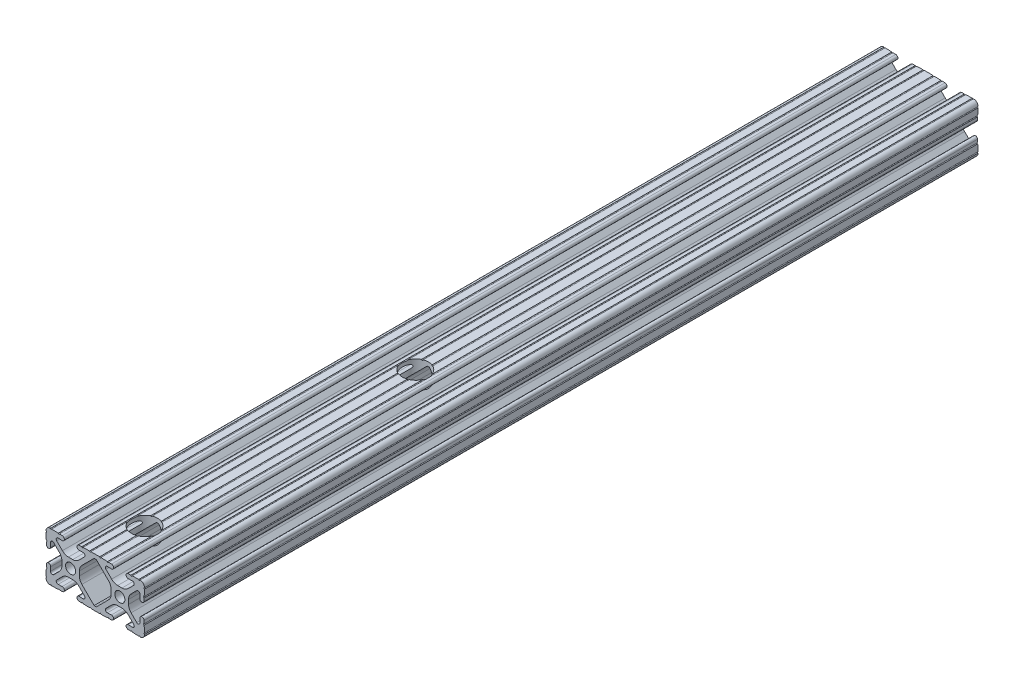
SolidWorks part; units mm, degrees
ref_plane "Front Plane" through (0, 0, 0) normal (0, 0, 1) x (1, 0, 0)
ref_plane "Top Plane" through (0, 0, 0) normal (0, 1, 0) x (1, 0, 0)
ref_plane "Right Plane" through (0, 0, 0) normal (1, 0, 0) x (0, 0, -1)
sketch "Sketch1" plane through (0, 0, 0) normal (0, 0, 1) x (1, 0, 0)
  line L0 (0, 12.7) -> (-12.7814, 12.7) construction
  line L1 (-4.5085, 0) -> (-4.5085, 2.9459)
  line L2 (-6.0437, 12.5461) -> (-10.0976, 12.6876) construction
  line L3 (-11.5616, 12.4229) -> (-4.3159, 12.1699) construction
  line L4 (-6.4364, 10.3486) -> (-6.3592, 12.5571) construction
  line L6 (-2.9459, 4.5085) -> (0, 4.5085)
  line L7 (0, 0) -> (0, 12.7) construction
  line L8 (0, 0) -> (-12.7814, 0) construction
  line L9 (0.7813, 0.7813) -> (-0.7813, -0.7813) construction
  line L10 (-2.9459, 4.5085) -> (-7.1484, 8.711)
  line L11 (-4.5085, 2.9459) -> (-8.711, 7.1484)
  line L13 (0, 0) -> (-12.7814, 12.7814) construction
  line L14 (-10.4131, 12.6987) -> (-4.3048, 12.4853)
  line L15 (-4.3048, 12.4853) -> (-4.382, 10.2769) construction
  line L16 (-4.382, 10.2769) -> (-6.4364, 10.3486)
  line L17 (-12.6987, 10.4131) -> (-12.4853, 4.3048)
  line L18 (-10.2769, 4.382) -> (-10.3486, 6.4364)
  circle A0 centre (0, 0) radius 2.6035
  arc A1 (-4.382, 10.2769) -> (-4.3048, 12.4853) centre (-4.3434, 11.3811) ccw
  arc A2 (-7.1484, 8.711) -> (-6.4364, 10.3486) centre (-6.4698, 9.3896) cw
  arc A3 (-8.711, 7.1484) -> (-10.3486, 6.4364) centre (-9.3896, 6.4698) ccw
  arc A4 (-10.2769, 4.382) -> (-12.4853, 4.3048) centre (-11.3811, 4.3434) cw
  arc A5 (-10.4131, 12.6987) -> (-12.6987, 10.4131) centre (-10.4902, 10.4902) ccw
  arc A6 (-10.4131, 12.6987) -> (-9.7821, 12.6766) centre (-10.0976, 12.6876) ccw
  arc A7 (-6.3592, 12.5571) -> (-5.7282, 12.5351) centre (-6.0437, 12.5461) ccw
  arc A8 (-12.5571, 6.3592) -> (-12.5351, 5.7282) centre (-12.5461, 6.0437) cw
  arc A9 (-12.6987, 10.4131) -> (-12.6766, 9.7821) centre (-12.6876, 10.0976) cw
  dimension "D1" = 5.207
  dimension "D5" = 14.859
  dimension "D9" = 2
  dimension "D2" = 25.4
  dimension "D12" = 0.6314
  dimension "D10" = 2.2098
  dimension "D3" = 9.017
  dimension "D4" = 9.017
  dimension "D6" = 25.4
  dimension "D7" = 6.477
  dimension "D8" = 2.2098
  dimension "D11" = 12.7
sketch "Sketch3" plane through (0, 0, 0) normal (0, 0, 1) x (1, 0, 0)
  line L0 (-2.9459, 4.5085) -> (0, 4.5085) construction
  line L1 (-2.9459, 4.5085) -> (-7.1484, 8.711) construction
  line L2 (-4.382, 10.2769) -> (-6.4364, 10.3486) construction
  line L3 (-10.4131, 12.6987) -> (-4.3048, 12.4853) construction
  line L4 (-4.5085, 0) -> (-4.5085, 2.9459) construction
  line L5 (-4.5085, 2.9459) -> (-8.711, 7.1484) construction
  line L6 (-10.2769, 4.382) -> (-10.3486, 6.4364) construction
  line L7 (-12.6987, 10.4131) -> (-12.4853, 4.3048) construction
  line L8 (-1.1153, 4.5085) -> (1.1153, 4.5085)
  line L9 (-4.2404, 5.803) -> (-7.1484, 8.711)
  line L10 (-4.382, 10.2769) -> (-6.4364, 10.3486)
  line L11 (-9.7821, 12.6766) -> (-6.3592, 12.5571)
  line L12 (-4.5085, -1.1153) -> (-4.5085, 1.1153)
  line L13 (-5.803, 4.2404) -> (-8.711, 7.1484)
  line L14 (-10.2769, 4.382) -> (-10.3486, 6.4364)
  line L15 (-12.6766, 9.7821) -> (-12.5571, 6.3592)
  line L16 (-5.7282, 12.5351) -> (-4.3048, 12.4853)
  line L17 (-12.5351, 5.7282) -> (-12.4853, 4.3048)
  line L18 (0, 0) -> (0, 12.7) construction
  line L19 (0, 0) -> (-12.7814, 0) construction
  line L20 (0, 0) -> (12.7, 0) construction
  line L21 (5.7282, 12.5351) -> (4.3048, 12.4853)
  line L22 (12.7, 10.5674) -> (12.7, 12.6987) construction
  line L23 (10.4131, 12.6987) -> (14.9869, 12.6987)
  line L24 (5.803, 4.2404) -> (12.1093, 10.5467)
  line L25 (4.5085, -1.1153) -> (4.5085, 1.1153)
  line L26 (9.7821, 12.6766) -> (6.3592, 12.5571)
  line L27 (4.382, 10.2769) -> (6.4364, 10.3486)
  line L28 (4.2404, 5.803) -> (7.1484, 8.711)
  line L29 (4.2404, -5.803) -> (7.1484, -8.711)
  line L30 (4.382, -10.2769) -> (6.4364, -10.3486)
  line L31 (9.7821, -12.6766) -> (6.3592, -12.5571)
  line L32 (5.803, -4.2404) -> (12.1093, -10.5467)
  line L33 (12.1093, 10.5467) -> (12.7, 10.5674)
  line L34 (10.4131, -12.6987) -> (14.9869, -12.6987)
  line L35 (5.7282, -12.5351) -> (4.3048, -12.4853)
  line L36 (12.7, -10.5674) -> (12.7, -12.6987) construction
  line L37 (-12.5351, -5.7282) -> (-12.4853, -4.3048)
  line L38 (-5.7282, -12.5351) -> (-4.3048, -12.4853)
  line L39 (-12.6766, -9.7821) -> (-12.5571, -6.3592)
  line L40 (-10.2769, -4.382) -> (-10.3486, -6.4364)
  line L41 (-5.803, -4.2404) -> (-8.711, -7.1484)
  line L42 (-9.7821, -12.6766) -> (-6.3592, -12.5571)
  line L43 (-4.382, -10.2769) -> (-6.4364, -10.3486)
  line L44 (-4.2404, -5.803) -> (-7.1484, -8.711)
  line L45 (-1.1153, -4.5085) -> (1.1153, -4.5085)
  line L46 (12.1093, -10.5467) -> (12.7, -10.5674)
  line L47 (13.2907, -10.5467) -> (12.7, -10.5674)
  line L48 (26.5153, -4.5085) -> (24.2847, -4.5085)
  line L49 (29.6404, -5.803) -> (32.5484, -8.711)
  line L50 (29.782, -10.2769) -> (31.8364, -10.3486)
  line L51 (35.1821, -12.6766) -> (31.7592, -12.5571)
  line L52 (31.203, -4.2404) -> (34.111, -7.1484)
  line L53 (35.6769, -4.382) -> (35.7486, -6.4364)
  line L54 (38.0766, -9.7821) -> (37.9571, -6.3592)
  line L55 (31.1282, -12.5351) -> (29.7048, -12.4853)
  line L56 (37.9351, -5.7282) -> (37.8853, -4.3048)
  line L57 (19.6718, -12.5351) -> (21.0952, -12.4853)
  line L58 (13.2907, 10.5467) -> (12.7, 10.5674)
  line L59 (19.597, -4.2404) -> (13.2907, -10.5467)
  line L60 (15.6179, -12.6766) -> (19.0408, -12.5571)
  line L61 (21.018, -10.2769) -> (18.9636, -10.3486)
  line L62 (21.1596, -5.803) -> (18.2516, -8.711)
  line L63 (21.1596, 5.803) -> (18.2516, 8.711)
  line L64 (21.018, 10.2769) -> (18.9636, 10.3486)
  line L65 (15.6179, 12.6766) -> (19.0408, 12.5571)
  line L66 (20.8915, -1.1153) -> (20.8915, 1.1153)
  line L67 (19.597, 4.2404) -> (13.2907, 10.5467)
  line L68 (19.6718, 12.5351) -> (21.0952, 12.4853)
  line L69 (37.9351, 5.7282) -> (37.8853, 4.3048)
  line L70 (31.1282, 12.5351) -> (29.7048, 12.4853)
  line L71 (38.0766, 9.7821) -> (37.9571, 6.3592)
  line L72 (35.6769, 4.382) -> (35.7486, 6.4364)
  line L73 (31.203, 4.2404) -> (34.111, 7.1484)
  line L74 (29.9085, -1.1153) -> (29.9085, 1.1153)
  line L75 (35.1821, 12.6766) -> (31.7592, 12.5571)
  line L76 (29.782, 10.2769) -> (31.8364, 10.3486)
  line L77 (29.6404, 5.803) -> (32.5484, 8.711)
  line L78 (26.5153, 4.5085) -> (24.2847, 4.5085)
  arc A0 (-10.4131, 12.6987) -> (-9.7821, 12.6766) centre (-10.0976, 12.6876) ccw construction
  arc A1 (-6.4364, 10.3486) -> (-7.1484, 8.711) centre (-6.4698, 9.3896) ccw construction
  arc A2 (-4.382, 10.2769) -> (-4.3048, 12.4853) centre (-4.3434, 11.3811) ccw construction
  arc A3 (-8.711, 7.1484) -> (-10.3486, 6.4364) centre (-9.3896, 6.4698) ccw construction
  arc A4 (-12.4853, 4.3048) -> (-10.2769, 4.382) centre (-11.3811, 4.3434) ccw construction
  arc A5 (-6.3592, 12.5571) -> (-5.7282, 12.5351) centre (-6.0437, 12.5461) ccw construction
  arc A6 (-10.4131, 12.6987) -> (-12.6987, 10.4131) centre (-10.4902, 10.4902) ccw construction
  arc A7 (-12.6766, 9.7821) -> (-12.6987, 10.4131) centre (-12.6876, 10.0976) ccw construction
  arc A8 (-12.5351, 5.7282) -> (-12.5571, 6.3592) centre (-12.5461, 6.0437) ccw construction
  arc A9 (-10.4131, 12.6987) -> (-9.7821, 12.6766) centre (-10.0976, 12.6876) ccw
  arc A10 (-6.4364, 10.3486) -> (-7.1484, 8.711) centre (-6.4698, 9.3896) ccw
  arc A11 (-4.382, 10.2769) -> (-4.3048, 12.4853) centre (-4.3434, 11.3811) ccw
  arc A12 (-8.711, 7.1484) -> (-10.3486, 6.4364) centre (-9.3896, 6.4698) ccw
  arc A13 (-12.4853, 4.3048) -> (-10.2769, 4.382) centre (-11.3811, 4.3434) ccw
  arc A14 (-6.3592, 12.5571) -> (-5.7282, 12.5351) centre (-6.0437, 12.5461) ccw
  arc A15 (-10.4131, 12.6987) -> (-12.6987, 10.4131) centre (-10.4902, 10.4902) ccw
  arc A16 (-12.6766, 9.7821) -> (-12.6987, 10.4131) centre (-12.6876, 10.0976) ccw
  arc A17 (-12.5351, 5.7282) -> (-12.5571, 6.3592) centre (-12.5461, 6.0437) ccw
  arc A18 (-1.1153, 4.5085) -> (-4.2404, 5.803) centre (-1.1153, 8.9281) cw
  arc A19 (4.5085, 1.1153) -> (5.803, 4.2404) centre (8.9281, 1.1153) cw
  arc A20 (1.1153, 4.5085) -> (4.2404, 5.803) centre (1.1153, 8.9281) ccw
  arc A21 (-4.5085, 1.1153) -> (-5.803, 4.2404) centre (-8.9281, 1.1153) ccw
  circle A22 centre (25.4, 0) radius 2.6035
  arc A23 (35.8131, -12.6987) -> (35.1821, -12.6766) centre (35.4976, -12.6876) ccw
  arc A24 (31.8364, -10.3486) -> (32.5484, -8.711) centre (31.8698, -9.3896) ccw
  arc A25 (6.3592, 12.5571) -> (5.7282, 12.5351) centre (6.0437, 12.5461) cw
  arc A26 (29.782, -10.2769) -> (29.7048, -12.4853) centre (29.7434, -11.3811) ccw
  arc A27 (34.111, -7.1484) -> (35.7486, -6.4364) centre (34.7896, -6.4698) ccw
  arc A28 (4.382, 10.2769) -> (4.3048, 12.4853) centre (4.3434, 11.3811) cw
  arc A29 (6.4364, 10.3486) -> (7.1484, 8.711) centre (6.4698, 9.3896) cw
  arc A30 (10.4131, 12.6987) -> (9.7821, 12.6766) centre (10.0976, 12.6876) cw
  arc A31 (10.4131, -12.6987) -> (9.7821, -12.6766) centre (10.0976, -12.6876) ccw
  arc A32 (6.4364, -10.3486) -> (7.1484, -8.711) centre (6.4698, -9.3896) ccw
  arc A33 (4.382, -10.2769) -> (4.3048, -12.4853) centre (4.3434, -11.3811) ccw
  arc A34 (37.8853, -4.3048) -> (35.6769, -4.382) centre (36.7811, -4.3434) ccw
  arc A35 (31.7592, -12.5571) -> (31.1282, -12.5351) centre (31.4437, -12.5461) ccw
  arc A36 (6.3592, -12.5571) -> (5.7282, -12.5351) centre (6.0437, -12.5461) ccw
  arc A37 (35.8131, -12.6987) -> (38.0987, -10.4131) centre (35.8902, -10.4902) ccw
  arc A38 (38.0766, -9.7821) -> (38.0987, -10.4131) centre (38.0876, -10.0976) ccw
  arc A39 (37.9351, -5.7282) -> (37.9571, -6.3592) centre (37.9461, -6.0437) ccw
  arc A40 (-4.5085, -1.1153) -> (-5.803, -4.2404) centre (-8.9281, -1.1153) cw
  arc A41 (1.1153, -4.5085) -> (4.2404, -5.803) centre (1.1153, -8.9281) cw
  arc A42 (4.5085, -1.1153) -> (5.803, -4.2404) centre (8.9281, -1.1153) ccw
  arc A43 (-1.1153, -4.5085) -> (-4.2404, -5.803) centre (-1.1153, -8.9281) ccw
  arc A44 (-12.5351, -5.7282) -> (-12.5571, -6.3592) centre (-12.5461, -6.0437) cw
  arc A45 (-12.6766, -9.7821) -> (-12.6987, -10.4131) centre (-12.6876, -10.0976) cw
  arc A46 (-10.4131, -12.6987) -> (-12.6987, -10.4131) centre (-10.4902, -10.4902) cw
  arc A47 (-6.3592, -12.5571) -> (-5.7282, -12.5351) centre (-6.0437, -12.5461) cw
  arc A48 (-12.4853, -4.3048) -> (-10.2769, -4.382) centre (-11.3811, -4.3434) cw
  arc A49 (-8.711, -7.1484) -> (-10.3486, -6.4364) centre (-9.3896, -6.4698) cw
  arc A50 (-4.382, -10.2769) -> (-4.3048, -12.4853) centre (-4.3434, -11.3811) cw
  arc A51 (-6.4364, -10.3486) -> (-7.1484, -8.711) centre (-6.4698, -9.3896) cw
  arc A52 (-10.4131, -12.6987) -> (-9.7821, -12.6766) centre (-10.0976, -12.6876) cw
  circle A53 centre (0, 0) radius 2.6035 construction
  circle A54 centre (0, 0) radius 2.6035
  arc A55 (26.5153, -4.5085) -> (29.6404, -5.803) centre (26.5153, -8.9281) cw
  arc A56 (20.8915, -1.1153) -> (19.597, -4.2404) centre (16.4719, -1.1153) cw
  arc A57 (24.2847, -4.5085) -> (21.1596, -5.803) centre (24.2847, -8.9281) ccw
  arc A58 (29.9085, -1.1153) -> (31.203, -4.2404) centre (34.3281, -1.1153) ccw
  arc A59 (19.0408, -12.5571) -> (19.6718, -12.5351) centre (19.3563, -12.5461) cw
  arc A60 (21.018, -10.2769) -> (21.0952, -12.4853) centre (21.0566, -11.3811) cw
  arc A61 (18.9636, -10.3486) -> (18.2516, -8.711) centre (18.9302, -9.3896) cw
  arc A62 (14.9869, -12.6987) -> (15.6179, -12.6766) centre (15.3024, -12.6876) cw
  arc A63 (14.9869, 12.6987) -> (15.6179, 12.6766) centre (15.3024, 12.6876) ccw
  arc A64 (18.9636, 10.3486) -> (18.2516, 8.711) centre (18.9302, 9.3896) ccw
  arc A65 (21.018, 10.2769) -> (21.0952, 12.4853) centre (21.0566, 11.3811) ccw
  arc A66 (19.0408, 12.5571) -> (19.6718, 12.5351) centre (19.3563, 12.5461) ccw
  arc A67 (29.9085, 1.1153) -> (31.203, 4.2404) centre (34.3281, 1.1153) cw
  arc A68 (24.2847, 4.5085) -> (21.1596, 5.803) centre (24.2847, 8.9281) cw
  arc A69 (20.8915, 1.1153) -> (19.597, 4.2404) centre (16.4719, 1.1153) ccw
  arc A70 (26.5153, 4.5085) -> (29.6404, 5.803) centre (26.5153, 8.9281) ccw
  arc A71 (37.9351, 5.7282) -> (37.9571, 6.3592) centre (37.9461, 6.0437) cw
  arc A72 (38.0766, 9.7821) -> (38.0987, 10.4131) centre (38.0876, 10.0976) cw
  arc A73 (35.8131, 12.6987) -> (38.0987, 10.4131) centre (35.8902, 10.4902) cw
  arc A74 (31.7592, 12.5571) -> (31.1282, 12.5351) centre (31.4437, 12.5461) cw
  arc A75 (37.8853, 4.3048) -> (35.6769, 4.382) centre (36.7811, 4.3434) cw
  arc A76 (34.111, 7.1484) -> (35.7486, 6.4364) centre (34.7896, 6.4698) cw
  arc A77 (29.782, 10.2769) -> (29.7048, 12.4853) centre (29.7434, 11.3811) cw
  arc A78 (31.8364, 10.3486) -> (32.5484, 8.711) centre (31.8698, 9.3896) cw
  arc A79 (35.8131, 12.6987) -> (35.1821, 12.6766) centre (35.4976, 12.6876) cw
  point P135 (4.5085, 0)
  point P218 (20.8915, 0)
  dimension "D2" = 4.4196
  dimension "D1" = 12.7
extrude "Extrude1" add sketch "Sketch3" along normal blind 430
sketch "Sketch4" plane through (0, 12.6987, 0) normal (0, 1, 0) x (1, 0, 0)
  line L0 (12.7, -430) -> (12.7, -404.6)
  line L1 (14.9869, -430) -> (10.4131, -430) construction
  line L2 (12.7, -404.6) -> (12.7, -264.9)
  circle A0 centre (12.7, -404.6) radius 6.75
  circle A1 centre (12.7, -264.9) radius 6.75
  line M2 (10.4131, 0) -> (10.4131, -430)
  line M4 (14.9869, -430) -> (14.9869, 0)
  dimension "D2" = 13.5
  dimension "D4" = 13.5
  dimension "D1" = 25.4
  dimension "D3" = 139.7
extrude "Cut-Extrude2" cut sketch "Sketch4" against normal through all contours A0 M4 | L0 A0 L2 M4 | A0 L0 L2 M2 | A0 M2 | A1 M4 | A1 M2 M4 | A1 M2 region at (11.568, 12.6987, 404.6) region at (13.832, 12.6987, 404.6) region at (8.565, 12.6987, 404.6) region at (16.835, 12.6987, 404.6) region at (11.5638, 12.6987, 271.409) region at (8.565, 12.6987, 264.9) region at (16.835, 12.6987, 264.9)
equation "\"D10@Sketch1\" = \"D8@Sketch1\""
equation "\"D11@Sketch1\" = \"D6@Sketch1\"/2"
equation "\"D12@Sketch1\" = \"D8@Sketch1\"/3.5"
equation "\"D2@Sketch3\" = \"D8@Sketch1\"*2"
